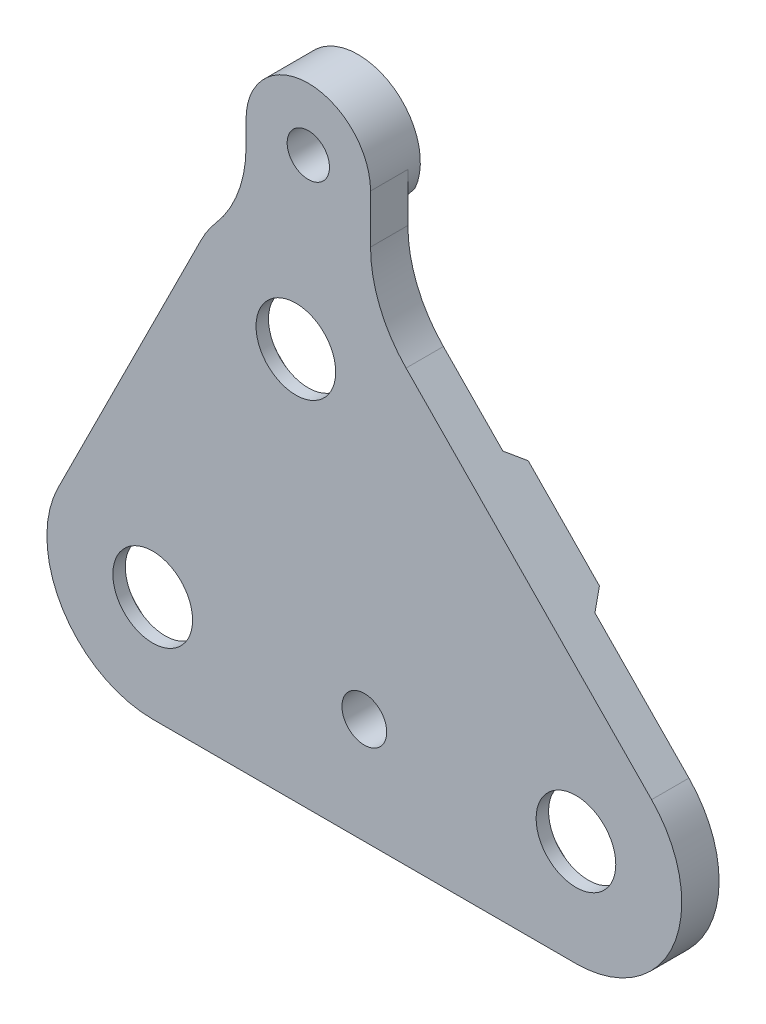
SolidWorks part; units mm, degrees
material "ABS"
ref_plane "Płaszczyzna przednia" through (0, 0, 0) normal (0, 0, 1) x (1, 0, 0)
ref_plane "Płaszczyzna górna" through (0, 0, 0) normal (0, 1, 0) x (1, 0, 0)
ref_plane "Płaszczyzna prawa" through (0, 0, 0) normal (1, 0, 0) x (0, 0, -1)
sketch "Szkic1" plane through (0, 0, 0) normal (0, 0, 1) x (1, 0, 0)
  line L0 (-7.6026, 3.8013) -> (3.8974, 26.8013)
  line L1 (17.5761, 28.944) -> (40.0761, 5.944)
  line L2 (34, -8.5) -> (25, -8.5)
  line L3 (22, -17) -> (22, -11.5)
  line L4 (12, -17) -> (12, -11.5)
  line L5 (9, -8.5) -> (0, -8.5)
  arc A0 (-7.6026, 3.8013) -> (0, -8.5) centre (0, 0) ccw
  arc A1 (17.5761, 28.944) -> (3.8974, 26.8013) centre (11.5, 23) ccw
  arc A2 (34, -8.5) -> (40.0761, 5.944) centre (34, 0) ccw
  circle A3 centre (17, 0) radius 1.8
  circle A4 centre (17, -17) radius 1.8
  arc A5 (12, -17) -> (22, -17) centre (17, -17) ccw
  arc A6 (12, -11.5) -> (9, -8.5) centre (9, -11.5) ccw
  arc A7 (22, -11.5) -> (25, -8.5) centre (25, -11.5) cw
  point P20 (12, -8.5)
  dimension "D1" = 17
  dimension "D2" = 17
  dimension "D3" = 3.6
  dimension "D4" = 34
  dimension "D5" = 17
  dimension "D6" = 23
  dimension "D7" = 17
  dimension "D8" = 11.5
  dimension "D10" = 23
  dimension "D11" = 17
  dimension "D12" = 3.6
  dimension "D14" = 5
  dimension "D15" = 3
  dimension "D9" = 23
  dimension "D13" = 17
extrude "Dodanie-wyciągnięcie1" add sketch "Szkic1" along normal blind 3
sketch "Szkic2" plane through (0, 0, 0) normal (0, 0, -1) x (-1, 0, 0)
  circle A0 centre (-34, 0) radius 6
  circle A1 centre (-11.5, 23) radius 6
  circle A2 centre (0, 0) radius 6
  dimension "D1" = 12
  dimension "D2" = 12
  dimension "D3" = 12
extrude "Wytnij-wyciągnięcie1" cut sketch "Szkic2" against normal blind 2
chamfer "Sfazowanie1" distance 0.5 angle 45 3 edges at (5.5, 23, 2) (-6, 0, 2) (28, 0, 2)
sketch "Szkic3" plane through (0, 0, 0) normal (0, 0, -1) x (-1, 0, 0)
  line L2 (-22, -17) -> (-22, 3.786)
  line L3 (-22.9021, 5.9305) -> (-31.6846, 14.522)
  line L4 (-25.9676, 20.366) -> (-16.0643, 10.678)
  line L5 (-40.0761, 5.944) -> (-17.5761, 28.944) construction
  line L6 (1.022, 16.9626) -> (-12.6248, 10.1392)
  line L7 (-3.8974, 26.8013) -> (7.6026, 3.8013) construction
  line L8 (2.6833, 13.64) -> (-10.3416, 7.1276)
  line L9 (-12, -17) -> (-12, 4.4443)
  line L10 (1.022, 16.9626) -> (2.6833, 13.64)
  line L11 (-25.9676, 20.366) -> (-31.6846, 14.522)
  arc A0 (-22, -17) -> (-12, -17) centre (-17, -17) ccw
  circle A2 centre (-17, 0) radius 1.8
  circle A3 centre (-17, -17) radius 1.8
  circle A4 centre (-34, 0) radius 5.5 construction
  circle A5 centre (-11.5, 23) radius 5.5 construction
  circle A6 centre (0, 0) radius 5.5 construction
  arc A7 (-10.3416, 7.1276) -> (-12, 4.4443) centre (-9, 4.4443) ccw
  arc A8 (-12.6248, 10.1392) -> (-16.0643, 10.678) centre (-13.9665, 12.8225) cw
  arc A9 (-22, 3.786) -> (-22.9021, 5.9305) centre (-25, 3.786) ccw
  dimension "D1" = 10
  dimension "D3" = 12
  dimension "D2" = 12
  dimension "D4" = 11
  dimension "D9" = 3
  dimension "D5" = 11
  dimension "D6" = 90
  dimension "D7" = 90
  dimension "D8" = 90
extrude "Dodanie-wyciągnięcie2" add sketch "Szkic3" along normal blind 1.2
chamfer "Sfazowanie2" distance 1.2 angle 45 9 edges at (12, -3.5279, 0) (22, -3.857, 0) (27.2933, 10.2262, 0) (22.2347, 4.9492, 0) (5.8014, 13.5509, 0) (14.4307, 9.8586, 0) (21.016, 15.522, 0) (3.8292, 10.3838, 0) (11.552, 6.0215, 0)
sketch "Szkic4" plane through (0, 0, -1.2) normal (0, 0, -1) x (-1, 0, 0)
  line L0 (-22, -12.1) -> (-12, -12.1)
  line L1 (-22, -12.1) -> (-22, -17)
  line L3 (-12, -12.1) -> (-12, -17)
  arc A0 (-22, -17) -> (-12, -17) centre (-17, -17) ccw
  circle A1 centre (-17, -17) radius 1.8
  dimension "D1" = 10
  dimension "D2" = 4.9
  dimension "D3" = 10
extrude "Dodanie-wyciągnięcie3" add sketch "Szkic4" along normal blind 5
sketch "Szkic5" plane through (0, 0, 3) normal (0, 0, 1) x (1, 0, 0)
  line L0 (7.5, 37) -> (7.5, 30.5)
  line L1 (17.5, 37) -> (17.5, 29.0208)
  line L2 (40.0761, 5.944) -> (17.5761, 28.944) construction
  line L3 (3.8974, 26.8013) -> (-7.6026, 3.8013) construction
  line L4 (40.0761, 5.944) -> (17.5761, 28.944)
  line L5 (3.8974, 26.8013) -> (-7.6026, 3.8013)
  circle A0 centre (12.5, 37) radius 1.7
  circle A1 centre (17, 0) radius 1.8 construction
  arc A2 (17.5, 37) -> (7.5, 37) centre (12.5, 37) ccw
  arc A3 (17.5761, 28.944) -> (3.8974, 26.8013) centre (11.5, 23) ccw construction
  arc A4 (17.5761, 28.944) -> (3.8974, 26.8013) centre (11.5, 23) ccw
  arc M11 (17.5761, 28.944) -> (3.8974, 26.8013) centre (11.5, 23) ccw
  dimension "D1" = 4.5
  dimension "D2" = 37
  dimension "D3" = 3.4
  dimension "D4" = 10
extrude "Dodanie-wyciągnięcie4" add sketch "Szkic5" against normal blind 3 contours L1 A2 L0 A0 M11 region at (12.5, 41.8362, 3)
sketch "Szkic6" plane through (0, 0, 0) normal (0, 0, -1) x (-1, 0, 0)
  line L6 (-13.1615, 11.2125) -> (0.4853, 18.0359)
  line L7 (0.4853, 18.0359) -> (-3.8974, 26.8013)
  line L8 (-7.5, 30.5) -> (-7.5, 37)
  line L9 (-17.5, 37) -> (-17.5, 29.0208)
  line L10 (-17.5761, 28.944) -> (-25.1285, 21.2238)
  line L11 (-25.1285, 21.2238) -> (-15.2252, 11.5358)
  line L12 (-13.1615, 11.2125) -> (0.4853, 18.0359)
  line L13 (0.4853, 18.0359) -> (-3.8974, 26.8013)
  line L14 (-7.5, 30.5) -> (-7.5, 37)
  line L15 (-17.5, 37) -> (-17.5, 29.0208)
  line L16 (-17.5761, 28.944) -> (-25.1285, 21.2238)
  line L17 (-25.1285, 21.2238) -> (-15.2252, 11.5358)
  circle A0 centre (-12.5, 37) radius 1.7 construction
  circle A1 centre (-12.5, 37) radius 1.7
  circle A2 centre (-12.5, 37) radius 5
  arc A4 (-15.2252, 11.5358) -> (-13.1615, 11.2125) centre (-13.9665, 12.8225) ccw
  arc A5 (-3.8974, 26.8013) -> (-7.5, 30.5) centre (-11.5, 23) ccw
  arc A6 (-7.5, 37) -> (-17.5, 37) centre (-12.5, 37) ccw
  arc A7 (-17.5, 29.0208) -> (-17.5761, 28.944) centre (-11.5, 23) ccw
  arc A8 (-15.2252, 11.5358) -> (-13.1615, 11.2125) centre (-13.9665, 12.8225) ccw
  arc A9 (-3.8974, 26.8013) -> (-7.5, 30.5) centre (-11.5, 23) ccw
  arc A10 (-7.5, 37) -> (-17.5, 37) centre (-12.5, 37) ccw
  arc A11 (-17.5, 29.0208) -> (-17.5761, 28.944) centre (-11.5, 23) ccw
  arc M17 (-7.5, 37) -> (-17.5, 37) centre (-12.5, 37) ccw
  circle M22 centre (-12.5, 37) radius 1.7
  dimension "D1" = 0
extrude "Dodanie-wyciągnięcie5" add sketch "Szkic6" along normal blind 1 contours A2 M17 M22 region at (12.5, 32.1414, 0)
fillet "Zaokrąglenie1" radius 10 2 edges at (17.5, 29.0208, 1.5) (7.5, 30.5, 1.5)
sketch "Szkic7" plane through (0, 0, -1) normal (0, 0, -1) x (-1, 0, 0)
  line L0 (-18.64, 34) -> (-5.2109, 34)
  line L1 (-5.2109, 34) -> (-5.2109, 29.218)
  line L2 (-5.2109, 29.218) -> (-18.64, 29.3541)
  line L3 (-18.64, 29.3541) -> (-18.64, 34)
  circle A0 centre (-12.5, 37) radius 1.7 construction
  dimension "D1" = 3
extrude "Wytnij-wyciągnięcie2" cut sketch "Szkic7" against normal up to surface (1 mm away) up to face at (28, 0, 0)
chamfer "Sfazowanie6" distance 1 angle 45 1 edges at (12.5, 34, -1)
sketch "Szkic8" plane through (12, 0, 0) normal (-1, 0, 0) x (0, 0, 1)
  line L0 (3, -8.5) -> (0, -8.5) construction
  line L1 (3, -8.5) -> (0, -8.5)
  line L2 (-9.4019, -8.5) -> (7.4574, -8.5)
  line L3 (7.4574, -8.5) -> (7.4574, -24.6682)
  line L4 (7.4574, -24.6682) -> (-9.4019, -24.6682)
  line L5 (-9.4019, -24.6682) -> (-9.4019, -8.5)
  line M1 (3, -11.5) -> (-1.2, -11.5)
  line M2 (-1.2, -11.5) -> (-1.2, -12.1)
  line M3 (-1.2, -12.1) -> (-6.2, -12.1)
  line M4 (-6.2, -12.1) -> (-6.2, -17)
  line M5 (-6.2, -17) -> (3, -17)
  line M6 (3, -17) -> (3, -11.5)
extrude "Wytnij-wyciągnięcie3" cut sketch "Szkic8" against normal blind 20 and the other way blind 10 contours L5 L4 L3 L2 L1 M1 M6 M5 M4 M3 M2 | M6 M1 M2 M3 M4 M5 region at (12, -17.0453, -0.8674) region at (12, -14.4044, -1.4676)
sketch "Szkic9" plane through (0, 0, 2) normal (0, 0, -1) x (-1, 0, 0)
  circle A0 centre (-34, 0) radius 3.2
  circle A1 centre (0, 0) radius 5.5
  circle A2 centre (0, 0) radius 5.5
  circle A3 centre (-11.5, 23) radius 5.5
  circle A4 centre (-11.5, 23) radius 5.5
  circle A5 centre (-34, 0) radius 5.5
  circle A6 centre (-34, 0) radius 5.5
  circle A7 centre (0, 0) radius 3.2
  circle A8 centre (-11.5, 23) radius 3.2
  dimension "D4" = 6.4
  dimension "D1" = 0
  dimension "D2" = 0
  dimension "D3" = 0
extrude "Wytnij-wyciągnięcie4" cut sketch "Szkic9" along direction (0, 0, -1) on the side against the normal blind 20 contours A0 | A7 | A8 region at (34, 0, 2) region at (0, 0, 2) region at (11.5, 23, 2)
